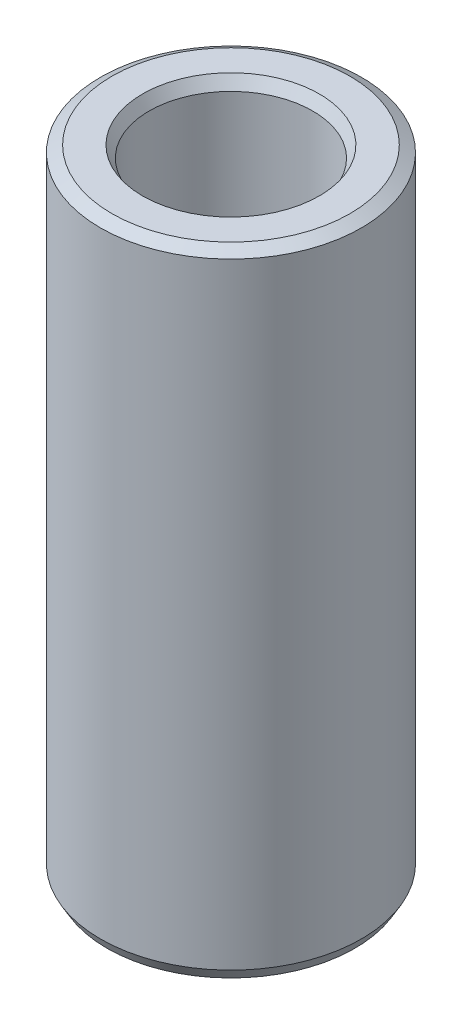
SolidWorks part; units mm, degrees
ref_plane "Front Plane" through (0, 0, 0) normal (0, 0, 1) x (1, 0, 0)
ref_plane "Top Plane" through (0, 0, 0) normal (0, 1, 0) x (1, 0, 0)
ref_plane "Right Plane" through (0, 0, 0) normal (1, 0, 0) x (0, 0, -1)
sketch "Sketch1" plane through (0, 0, 0) normal (0, 1, 0) x (1, 0, 0)
  circle A0 centre (0, 0) radius 27.5
  dimension "SLEEVE_OD" = 55
extrude "Boss-Extrude1" add sketch "Sketch1" along normal blind 133.564
sketch "Sketch2" plane through (0, 0, 0) normal (0, 1, 0) x (1, 0, 0)
  circle A0 centre (0, 0) radius 17.2324
  dimension "BORE_D" = 34.4647
extrude "Cut-Extrude1" cut sketch "Sketch2" along normal through all
chamfer "Chamfer1" distance 1.3936 angle 60 4 edges at (0, 133.564, 17.2324) (0, 0, 17.2324) (0, 0, 27.5) (0, 133.564, 27.5) first distance on face at (0, 133.564, 17.2324) first distance on face at (0, 0, 17.2324) first distance on face at (0, 133.564, 27.5)
